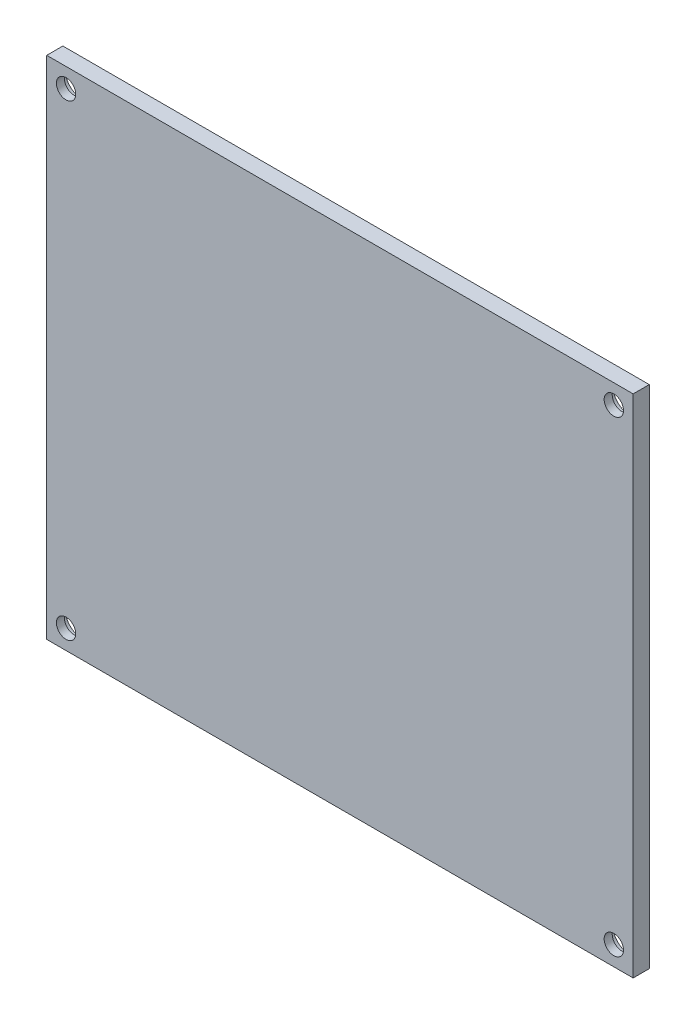
SolidWorks part; units mm, degrees
ref_plane "Front Plane" through (0, 0, 0) normal (0, 0, 1) x (1, 0, 0)
ref_plane "Top Plane" through (0, 0, 0) normal (0, 1, 0) x (1, 0, 0)
ref_plane "Right Plane" through (0, 0, 0) normal (1, 0, 0) x (0, 0, -1)
sketch "Sketch1" plane through (0, 0, 0) normal (0, 0, 1) x (1, 0, 0)
  line L16 (131.9912, -26.2639) -> (131.9912, 36.5361)
  line L17 (59.1912, -26.2639) -> (131.9912, -26.2639)
  line L18 (59.1912, 36.5361) -> (59.1912, -26.2639)
  line L19 (131.9912, 36.5361) -> (59.1912, 36.5361)
  line L20 (131.9912, -26.2639) -> (131.9912, 36.5361)
  line L21 (59.1912, -26.2639) -> (131.9912, -26.2639)
  line L22 (59.1912, 36.5361) -> (59.1912, -26.2639)
  line L23 (131.9912, 36.5361) -> (59.1912, 36.5361)
  dimension "D1" = 0.1
extrude "Boss-Extrude1" add sketch "Sketch1" along normal blind 2
hole_wizard "CBORE for M2 Pan Head Machine Screw1" positions "Sketch4" profile "Sketch3" counterbore size "M2" standard "ANSI Metric"
sketch "Sketch4" plane through (0, 0, 0) normal (0, 0, -1) x (-1, 0, 0)
  point P0 (-129.5912, 34.1361)
  point P3 (-61.5912, 34.1361)
  point P6 (-61.5912, -23.8639)
  point P9 (-129.5912, -23.8639)
sketch "Sketch3" plane through (129.5912, 34.1361, 0) normal (1, 0, 0) x (0, 1, 0)
  line L0 (0, 0) -> (0, 6.721)
  line L1 (0, 6.721) -> (1.2, 6)
  line L2 (1.2, 6) -> (1.2, 1)
  line L3 (1.2, 1) -> (2.125, 1)
  line L4 (2.125, 1) -> (2.125, 0)
  line L5 (2.125, 0) -> (0, 0)
  line L10 (0, 6.721) -> (-1.2, 6) construction
  line L11 (0, -6.35) -> (0, 107.95) construction
  dimension "Hole Dia." = 2.4
  dimension "Hole Depth" = 6
  dimension "C'Bore Dia." = 4.25
  dimension "C'Bore Depth" = 1
  dimension "Drill Angle" = 118
